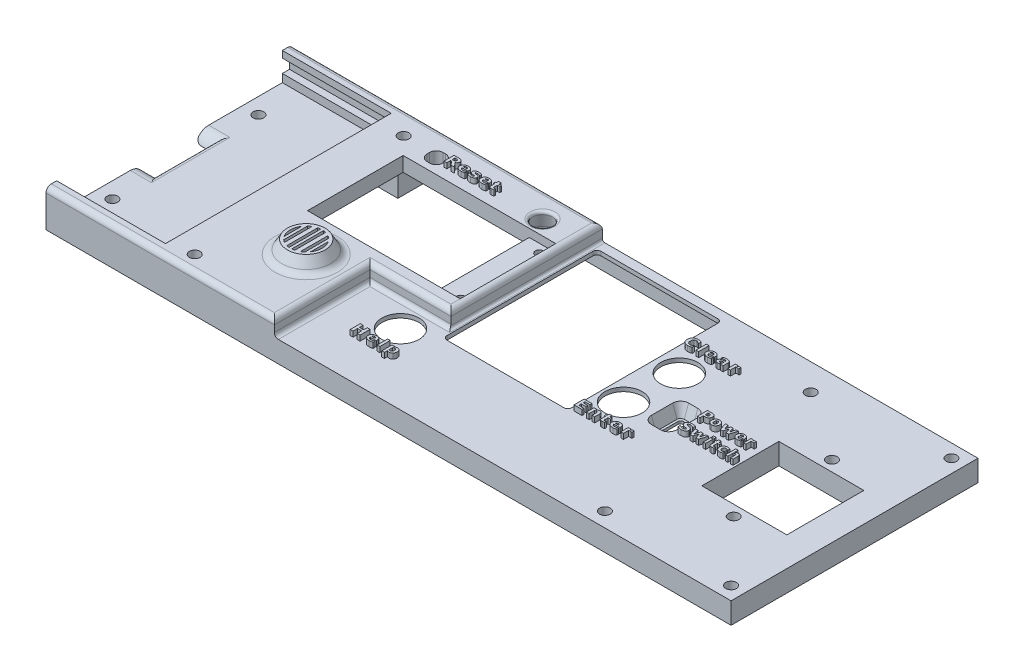
SolidWorks part; units mm, degrees
ref_plane "Front Plane" through (0, 0, 0) normal (0, 0, 1) x (1, 0, 0)
ref_plane "Top Plane" through (0, 0, 0) normal (0, 1, 0) x (1, 0, 0)
ref_plane "Right Plane" through (0, 0, 0) normal (1, 0, 0) x (0, 0, -1)
sketch "Sketch1" plane through (0, 0, 0) normal (0, 1, 0) x (1, 0, 0)
  line L1 (-85, -46.5) -> (85, -46.5)
  line L2 (-85, -46.5) -> (-85, 46.5)
  line L3 (-85, 46.5) -> (85, 46.5)
  line L4 (85, -46.5) -> (85, 46.5)
  line L5 (-85, -46.5) -> (85, 46.5) construction
  line L6 (-85, 46.5) -> (85, -46.5) construction
  point P0 (0, 0)
  dimension "D1" = 170
  dimension "D2" = 93
extrude "Base_01" add sketch "Sketch1" along normal blind 5
sketch "Sketch2" plane through (0, 5, 0) normal (0, 1, 0) x (1, 0, 0)
  line L0 (85, 46.5) -> (-85, 46.5) construction
  line L1 (-10, 46.5) -> (41, 46.5) construction
  line L2 (-10, 46.5) -> (-10, -18.5) construction
  line L3 (-10, -18.5) -> (41, -18.5) construction
  line L4 (41, 46.5) -> (41, -18.5) construction
  line L5 (85, -46.5) -> (85, 46.5) construction
  line L6 (-10, -18.5) -> (41, 46.5) construction
  line L8 (-8, 43) -> (39, 43)
  line L9 (-8, 43) -> (-8, -15)
  line L10 (-8, -15) -> (39, -15)
  line L11 (39, 43) -> (39, -15)
  line L12 (-8, 43) -> (39, -15) construction
  line L13 (-8, -15) -> (39, 43) construction
  point P8 (15.5, 14)
  dimension "D1" = 95
  dimension "D2" = 65
  dimension "D3" = 51
  dimension "D4" = 58
  dimension "D5" = 47
extrude "Keypad" cut sketch "Sketch2" against normal through all
fillet "Keypad_Fillet" radius 1.5 4 edges at (39, 2.5, 15) (-8, 2.5, 15) (-8, 2.5, -43) (39, 2.5, -43)
sketch "Sketch3" plane through (0, 5, 0) normal (0, 1, 0) x (1, 0, 0)
  line L0 (-8, 41.5) -> (-8, -13.5) construction
  line L7 (85, 46.5) -> (-85, 46.5) construction
  line L8 (85, -46.5) -> (85, 46.5) construction
  line L9 (-85, -46.5) -> (85, -46.5) construction
  circle A0 centre (48, 18) radius 7
  circle A1 centre (47, -2) radius 7
  circle A2 centre (-19, -20) radius 7
  point P9 (55, 18)
  point P10 (54, -2)
  point P11 (48, 25)
  point P12 (48, 11)
  point P13 (47, 5)
  point P14 (47, -9)
  point P23 (-26, -20)
  point P26 (-19, -13)
  dimension "D2" = 14
  dimension "D1" = 63
  dimension "D3" = 62
  dimension "D4" = 55.5
  dimension "D5" = 34
  dimension "D6" = 111
  dimension "D7" = 33.5
extrude "Buttons" cut sketch "Sketch3" against normal through all
sketch "Sketch4" plane through (0, 0, 0) normal (0, -1, 0) x (1, 0, 0)
  line L0 (-85, 46.5) -> (85, 46.5) construction
  line L1 (-80, 43) -> (80.5, 43)
  line L2 (-80, 43) -> (-80, -45)
  line L3 (-80, -45) -> (80.5, -45)
  line L4 (80.5, 43) -> (80.5, -45)
  line L5 (85, 46.5) -> (85, -46.5) construction
  line L6 (85, -46.5) -> (-85, -46.5) construction
  line L7 (-85, -46.5) -> (-85, 46.5) construction
  dimension "D1" = 3.5
  dimension "D2" = 4.5
  dimension "D3" = 1.5
  dimension "D4" = 5
extrude "Base_01_Ext_Cut" cut sketch "Sketch4" against normal blind 3.5
sketch "Sketch5" plane through (0, 5, 0) normal (0, 1, 0) x (1, 0, 0)
  line L0 (39, -13.5) -> (39, 41.5) construction
  line L1 (-66, 26.0978) -> (-10, 26.0978) construction
  line L2 (-66, 26.0978) -> (-66, -7.5) construction
  line L3 (-66, -7.5) -> (-10, -7.5) construction
  line L4 (-10, 26.0978) -> (-10, -7.5) construction
  line L5 (85, 46.5) -> (-85, 46.5) construction
  line L6 (-10, 26.0978) -> (-10, 46.5)
  line L7 (-8, 46.5) -> (-8, 41.5691) construction
  line L8 (-8, 41.5) -> (-8, -13.5) construction
  line L9 (-9.5, 46.5) -> (-9.5, -10.5)
  line L10 (-9.5, -10.5) -> (-40, -10.5)
  line L11 (-40, -10.5) -> (-40, -46.5)
  line L12 (-85, -46.5) -> (85, -46.5) construction
  line L13 (-40, -46.5) -> (-85, -46.5)
  line L14 (-85, -46.5) -> (-85, 46.5)
  line L15 (-85, 46.5) -> (-85, -46.5) construction
  line L16 (-85, 46.5) -> (-9.5, 46.5)
  dimension "D1" = 105
  dimension "D2" = 56
  dimension "D3" = 54
  dimension "D4" = 75.5
  dimension "D5" = 3
  dimension "D6" = 45
extrude "Base_02" add sketch "Sketch5" along normal blind 6
fillet "Fillet2" radius 1 1 edges at (-9.5, 5, -18)
fillet "Fillet3" radius 1.5 2 edges at (-40, 5, 28.5) (-24.25, 5, 10.5)
fillet "Base_02_Fillet" radius 2 6 edges at (-62.5, 11, 46.5) (-85, 11, 0) (-47.25, 11, -46.5) (-9.5, 11, -18) (-24.75, 11, 10.5) (-40, 11, 28.5)
sketch "Sketch7" plane through (0, 11, 0) normal (0, 1, 0) x (1, 0, 0)
  line L0 (39, -13.5) -> (39, 41.5) construction
  line L1 (-69, -5) -> (-11.5, -5)
  line L2 (-69, -5) -> (-69, 31)
  line L3 (-69, 31) -> (-11.5, 31)
  line L4 (-11.5, -5) -> (-11.5, 31)
  line L5 (-69, -5) -> (-11.5, 31) construction
  line L6 (-69, 31) -> (-11.5, -5) construction
  line L7 (-65, 33.5) -> (-59, 33.5)
  line L8 (-65, 33.5) -> (-65, 39.5)
  line L9 (-65, 39.5) -> (-59, 39.5)
  line L10 (-59, 33.5) -> (-59, 39.5)
  line L11 (-65, 33.5) -> (-59, 39.5) construction
  line L12 (-65, 39.5) -> (-59, 33.5) construction
  line L13 (-38.5, -46.5) -> (85, -46.5) construction
  line L15 (-85, 46.5) -> (-9.5, 46.5) construction
  line L16 (-85, -46.5) -> (-85, 46.5) construction
  point P0 (-40.25, 13)
  point P5 (-62, 36.5)
  dimension "D1" = 57.5
  dimension "D2" = 108
  dimension "D3" = 36
  dimension "D4" = 77.5
  dimension "D5" = 6
  dimension "D6" = 13
  dimension "D7" = 26
extrude "Display & Reset" cut sketch "Sketch7" against normal through all
fillet "Reset_Fillet" radius 2.5 4 edges at (-65, 7.25, -33.5) (-65, 7.25, -39.5) (-59, 7.25, -33.5) (-59, 7.25, -39.5)
ref_plane "Display Support Plane" through (0, 8, 0) normal (0, 1, 0) x (1, 0, 0)
sketch "Sketch8" plane through (0, 8, 0) normal (0, 1, 0) x (1, 0, 0)
  line L0 (-11.5, 31) -> (-69, 31) construction
  line L1 (-21.5, 31) -> (-11.5, 31)
  line L2 (-21.5, 31) -> (-21.5, -5)
  line L3 (-21.5, -5) -> (-11.5, -5)
  line L4 (-11.5, 31) -> (-11.5, -5)
  dimension "D1" = 10
extrude "Display_Support" add sketch "Sketch8" against normal up to surface (4.5 mm away) up to face at (-40.25, 3.5, -13)
sketch "Sketch10" plane through (0, 8, 0) normal (0, 1, 0) x (1, 0, 0)
  line L1 (-69, 31) -> (-69, -5) construction
  line L2 (-11.5, 31) -> (-69, 31) construction
  line L3 (-11.5, 13) -> (-21.5, 13) construction
  line L4 (-11.5, -5) -> (-11.5, 31) construction
  line L5 (-21.5, 31) -> (-21.5, -5) construction
  circle A0 centre (-14.5, 27.8) radius 1.5
  circle A2 centre (-14.5, -1.8) radius 1.5
  point P6 (-13, 27.8)
  point P7 (-14.5, 26.3)
  dimension "D1" = 3
  dimension "D2" = 4.7
  dimension "5.5" = 56
extrude "Display Support holes" cut sketch "Sketch10" against normal through all
sketch "Sketch9" plane through (0, 3.5, 0) normal (0, -1, 0) x (1, 0, 0)
  line L0 (-9.5, -45) -> (-80, -45)
  line L1 (-80, -45) -> (80.5, -45) construction
  line L2 (-80, -45) -> (-80, 43)
  line L3 (80.5, 43) -> (-80, 43) construction
  line L4 (-80, 43) -> (-80, -45) construction
  line L5 (-80, 43) -> (-40, 43)
  line L6 (-9.5, 10.5) -> (-40, 10.5)
  line L7 (-40, 10.5) -> (-40, 46.5)
  line L8 (-40, 46.5) -> (-85, 46.5)
  line L9 (-85, 46.5) -> (-85, -46.5)
  line L10 (-85, -46.5) -> (-9.5, -46.5)
  line L11 (-9.5, -46.5) -> (-9.5, 10.5)
  line L12 (-9.5, 10.5) -> (-40, 10.5)
  line L17 (-9.5, -46.5) -> (-9.5, 10.5)
  line L18 (-40, 43) -> (-40, 10.5)
  line M7 (-69, 5) -> (-21.5, 5)
  line M8 (-21.5, 5) -> (-21.5, -31)
  line M9 (-21.5, -31) -> (-69, -31)
  line M10 (-69, -31) -> (-69, 5)
  line M11 (-59, -36) -> (-59, -37)
  arc M12 (-59, -37) -> (-61.5, -39.5) centre (-61.5, -37) cw
  line M13 (-61.5, -39.5) -> (-62.5, -39.5)
  arc M14 (-62.5, -39.5) -> (-65, -37) centre (-62.5, -37) cw
  line M15 (-65, -37) -> (-65, -36)
  arc M16 (-65, -36) -> (-62.5, -33.5) centre (-62.5, -36) cw
  line M17 (-62.5, -33.5) -> (-61.5, -33.5)
  arc M18 (-61.5, -33.5) -> (-59, -36) centre (-61.5, -36) cw
  line M22 (-80, 43) -> (-80, -45)
  line M23 (-80, -45) -> (80.5, -45)
  line M25 (80.5, 43) -> (-80, 43)
  dimension "D1" = 0
extrude "Base_02_Ext_Cut" cut sketch "Sketch9" against normal blind 2 contours L18 L17 L12 M25 M22 M23 M18 M11 M12 M13 M14 M15 M16 M17 M10 M7 M8 M9
sketch "Sketch11" plane through (0, 11, 0) normal (0, 1, 0) x (1, 0, 0)
  line L0 (-40, -46.5) -> (-85, -46.5) construction
  line L1 (-85, -46.5) -> (-85, 46.5) construction
  line L2 (-55, -13.5) -> (-55, -25.5) construction
  line L3 (-54.5, -13.5209) -> (-54.5, -25.4791)
  line L4 (-52, -14.3038) -> (-52, -24.6962)
  line L5 (-50, -16.1834) -> (-50, -22.8166)
  line L6 (-53.5, -13.6905) -> (-53.5, -25.3095)
  line L7 (-51, -15.0279) -> (-51, -23.9721)
  line L8 (-60, -16.1834) -> (-60, -22.8166)
  line L9 (-59, -15.0279) -> (-59, -23.9721)
  line L10 (-58, -14.3038) -> (-58, -24.6962)
  line L11 (-56.5, -13.6905) -> (-56.5, -25.3095)
  line L12 (-55.5, -13.5209) -> (-55.5, -25.4791)
  arc A0 (-51, -15.0279) -> (-52, -14.3038) centre (-55, -19.5) ccw
  arc A1 (-50, -22.8166) -> (-50, -16.1834) centre (-55, -19.5) ccw
  arc A2 (-52, -24.6962) -> (-51, -23.9721) centre (-55, -19.5) ccw
  arc A3 (-53.5, -13.6905) -> (-54.5, -13.5209) centre (-55, -19.5) ccw
  arc A4 (-55.5, -13.5209) -> (-56.5, -13.6905) centre (-55, -19.5) ccw
  arc A5 (-54.5, -25.4791) -> (-53.5, -25.3095) centre (-55, -19.5) ccw
  arc A6 (-56.5, -25.3095) -> (-55.5, -25.4791) centre (-55, -19.5) ccw
  arc A7 (-59, -23.9721) -> (-58, -24.6962) centre (-55, -19.5) ccw
  arc A8 (-60, -16.1834) -> (-60, -22.8166) centre (-55, -19.5) ccw
  arc A9 (-58, -14.3038) -> (-59, -15.0279) centre (-55, -19.5) ccw
  point P2 (-55, -13.5)
  point P5 (-49, -19.5)
  dimension "D3" = 12
  dimension "D1" = 33
  dimension "D2" = 36
  dimension "D4" = 0.5
  dimension "D5" = 2.5
  dimension "D6" = 1
  dimension "D7" = 1
  dimension "D8" = 2
extrude "Cut-Extrude7" cut sketch "Sketch11" against normal through all contours L3 A5 L6 A3 | L4 A2 L7 A0 | L5 A1 | L11 A6 L12 A4 | L10 A9 L9 A7 | L8 A8
ref_plane "Support Speaker Plane" through (0, 0, 0) normal (0, -1, 0) x (-1, 0, 0)
sketch "Sketch15" plane through (0, 11, 0) normal (0, 1, 0) x (1, 0, 0)
  circle A0 centre (-55, -19.5) radius 10
  point P0 (-55, -19.5)
  dimension "D1" = 20
extrude "Speaker_Extrude" add sketch "Sketch15" along normal blind 5 draft 30
sketch "Sketch16" plane through (0, 16, 0) normal (0, 1, 0) x (1, 0, 0)
  line L1 (-50, -16.1834) -> (-50, -22.8166)
  line L2 (-50, -16.1834) -> (-50, -22.8166)
  line L3 (-60, -22.8166) -> (-60, -16.1834)
  line L4 (-56.5, -13.6905) -> (-56.5, -25.3095)
  line L5 (-55.5, -25.4791) -> (-55.5, -13.5209)
  line L6 (-56.5, -13.6905) -> (-56.5, -25.3095)
  line L7 (-55.5, -25.4791) -> (-55.5, -13.5209)
  line L8 (-59, -15.0279) -> (-59, -23.9721)
  line L9 (-58, -24.6962) -> (-58, -14.3038)
  line L10 (-59, -15.0279) -> (-59, -23.9721)
  line L11 (-58, -24.6962) -> (-58, -14.3038)
  line L12 (-60, -22.8166) -> (-60, -16.1834)
  line L14 (-51, -23.9721) -> (-51, -15.0279)
  line L15 (-52, -14.3038) -> (-52, -24.6962)
  line L16 (-51, -23.9721) -> (-51, -15.0279)
  line L17 (-52, -14.3038) -> (-52, -24.6962)
  line L18 (-53.5, -25.3095) -> (-53.5, -13.6905)
  line L19 (-54.5, -13.5209) -> (-54.5, -25.4791)
  line L20 (-53.5, -25.3095) -> (-53.5, -13.6905)
  line L21 (-54.5, -13.5209) -> (-54.5, -25.4791)
  arc A1 (-50, -22.8166) -> (-50, -16.1834) centre (-55, -19.5) ccw
  arc A2 (-50, -22.8166) -> (-50, -16.1834) centre (-55, -19.5) ccw
  arc A3 (-60, -16.1834) -> (-60, -22.8166) centre (-55, -19.5) ccw
  arc A4 (-56.5, -25.3095) -> (-55.5, -25.4791) centre (-55, -19.5) ccw
  arc A5 (-55.5, -13.5209) -> (-56.5, -13.6905) centre (-55, -19.5) ccw
  arc A6 (-56.5, -25.3095) -> (-55.5, -25.4791) centre (-55, -19.5) ccw
  arc A7 (-55.5, -13.5209) -> (-56.5, -13.6905) centre (-55, -19.5) ccw
  arc A8 (-59, -23.9721) -> (-58, -24.6962) centre (-55, -19.5) ccw
  arc A9 (-58, -14.3038) -> (-59, -15.0279) centre (-55, -19.5) ccw
  arc A10 (-59, -23.9721) -> (-58, -24.6962) centre (-55, -19.5) ccw
  arc A11 (-58, -14.3038) -> (-59, -15.0279) centre (-55, -19.5) ccw
  arc A12 (-60, -16.1834) -> (-60, -22.8166) centre (-55, -19.5) ccw
  arc A14 (-52, -24.6962) -> (-51, -23.9721) centre (-55, -19.5) ccw
  arc A15 (-51, -15.0279) -> (-52, -14.3038) centre (-55, -19.5) ccw
  arc A16 (-52, -24.6962) -> (-51, -23.9721) centre (-55, -19.5) ccw
  arc A17 (-51, -15.0279) -> (-52, -14.3038) centre (-55, -19.5) ccw
  arc A18 (-54.5, -25.4791) -> (-53.5, -25.3095) centre (-55, -19.5) ccw
  arc A19 (-53.5, -13.6905) -> (-54.5, -13.5209) centre (-55, -19.5) ccw
  arc A20 (-54.5, -25.4791) -> (-53.5, -25.3095) centre (-55, -19.5) ccw
  arc A21 (-53.5, -13.6905) -> (-54.5, -13.5209) centre (-55, -19.5) ccw
  dimension "D1" = 0
  dimension "D2" = 0
  dimension "D3" = 0
  dimension "D4" = 0
  dimension "D5" = 0
  dimension "D6" = 0
extrude "Grid_Ext_Cut" cut sketch "Sketch16" against normal through all
sketch "Sketch17" plane through (0, 5.5, 0) normal (0, -1, 0) x (1, 0, 0)
  circle A1 centre (-55, 19.5) radius 10
  circle A2 centre (-55, 19.5) radius 10
  dimension "D1" = 0
extrude "Lower_Side_Cut" cut sketch "Sketch17" against normal blind 3 draft 35 draft outward yes
fillet "Side_Fillet" radius 3 1 edges at (-55, 11, 29.5)
sketch "Sketch24" plane through (0, 8.5, 0) normal (0, -1, 0) x (1, 0, 0)
  circle A0 centre (-55, 19.5) radius 7.5
  circle A1 centre (-55, 19.5) radius 10
  circle A2 centre (-55, 19.5) radius 10 construction
  line M3 (-52, 14.3038) -> (-52, 24.6962)
  arc M4 (-52, 24.6962) -> (-51, 23.9721) centre (-55, 19.5) cw
  line M5 (-51, 23.9721) -> (-51, 15.0279)
  arc M6 (-51, 15.0279) -> (-52, 14.3038) centre (-55, 19.5) cw
  line M7 (-56.5, 13.6905) -> (-56.5, 25.3095)
  arc M8 (-56.5, 25.3095) -> (-55.5, 25.4791) centre (-55, 19.5) cw
  line M9 (-55.5, 25.4791) -> (-55.5, 13.5209)
  arc M10 (-55.5, 13.5209) -> (-56.5, 13.6905) centre (-55, 19.5) cw
  arc M11 (-58, 14.3038) -> (-59, 15.0279) centre (-55, 19.5) cw
  line M12 (-59, 15.0279) -> (-59, 23.9721)
  arc M13 (-59, 23.9721) -> (-58, 24.6962) centre (-55, 19.5) cw
  line M14 (-58, 24.6962) -> (-58, 14.3038)
  arc M15 (-60, 16.1834) -> (-60, 22.8166) centre (-55, 19.5) cw
  line M16 (-60, 22.8166) -> (-60, 16.1834)
  line M18 (-50, 16.1834) -> (-50, 22.8166)
  arc M19 (-50, 22.8166) -> (-50, 16.1834) centre (-55, 19.5) cw
  line M20 (-54.5, 13.5209) -> (-54.5, 25.4791)
  arc M21 (-54.5, 25.4791) -> (-53.5, 25.3095) centre (-55, 19.5) cw
  line M22 (-53.5, 25.3095) -> (-53.5, 13.6905)
  arc M23 (-53.5, 13.6905) -> (-54.5, 13.5209) centre (-55, 19.5) cw
  dimension "D2" = 15
  dimension "D1" = 0
extrude "Cut-Extrude13" cut sketch "Sketch24" against normal offset from surface (6.5 mm away) 1 contours A0 M6 M3 M4 M5 M10 M7 M8 M9 M14 M11 M12 M13 M16 M15 M23 M20 M21 M22 M19 M18 up to face at (-49.5, 16, 19.5)
fillet "Fillet7" radius 5 1 edges at (-55, 8.5, 12)
fillet "Fillet8" radius 1 1 edges at (-55, 5.5, 9.5)
sketch "Sketch18" plane through (0, 11, 0) normal (0, 1, 0) x (1, 0, 0)
  line L2 (-59, 36) -> (-59, 37) construction
  line L3 (39, -13.5) -> (39, 41.5) construction
  circle A0 centre (-22, 36.5) radius 3.5
  point P4 (-18.5, 36.5)
  point P8 (-59, 36.5)
  point P9 (-25.5, 36.5)
  dimension "D2" = 7
  dimension "D1" = 64.5
extrude "Indicator" cut sketch "Sketch18" against normal up to surface (5.5 mm away) draft 10
sketch "Sketch20" plane through (0, 5, 0) normal (0, 1, 0) x (1, 0, 0)
  line L0 (-38.5, -46.5) -> (85, -46.5) construction
  line L1 (59, 7.5) -> (63.5, 7.5)
  line L2 (59, 7.5) -> (59, -1.5)
  line L3 (59, -1.5) -> (63.5, -1.5)
  line L4 (63.5, 7.5) -> (63.5, -1.5)
  line L5 (59, 7.5) -> (63.5, -1.5) construction
  line L6 (59, -1.5) -> (63.5, 7.5) construction
  line L7 (85, -46.5) -> (85, 46.5) construction
  point P0 (59, 3)
  dimension "D4" = 26
  dimension "D1" = 54
  dimension "D2" = 9
  dimension "D3" = 4.5
extrude "Power Switch" cut sketch "Sketch20" against normal through all
sketch "Sketch25" plane through (85, 0, 0) normal (1, 0, 0) x (0, 0, -1)
  line L4 (-46.5, 0) -> (46.5, 0)
  line L5 (46.5, 0) -> (46.5, 5)
  line L6 (46.5, 5) -> (-46.5, 5)
  line L7 (-46.5, 5) -> (-46.5, 0)
  line L9 (46.5, 0) -> (46.5, 5)
  line L10 (46.5, 5) -> (-46.5, 5)
  line L11 (-46.5, 5) -> (-46.5, 0)
  line L13 (-46.5, 0) -> (46.5, 0)
  dimension "D1" = 0
extrude "Base_Support_01" add sketch "Sketch25" along normal blind 2
sketch "Sketch26" plane through (0, 0, 0) normal (0, -1, 0) x (1, 0, 0)
  line L0 (-80, -45) -> (80.5, -45) construction
  line L1 (-9.5, -45) -> (80.5, -45) construction
  line L2 (80.5, -45) -> (80.5, 43) construction
  line L3 (80.5, 43) -> (-80, 43) construction
  line L4 (-85, -46.5) -> (87, -46.5)
  line L5 (87, -46.5) -> (87, 46.5)
  line L6 (87, 46.5) -> (-85, 46.5)
  line L7 (-85, 46.5) -> (-85, -46.5)
  line L8 (-85, -46.5) -> (87, -46.5)
  line L10 (87, 46.5) -> (-85, 46.5)
  line L11 (-85, 46.5) -> (-85, -46.5)
  line L12 (-80, 43) -> (-80, -45) construction
  line L13 (-80, -45) -> (80.5, -45)
  line L14 (-9.5, -45) -> (80.5, -45)
  line L15 (80.5, -45) -> (80.5, 43)
  line L16 (80.5, 43) -> (-80, 43)
  line L17 (-80, 43) -> (-80, -45)
  line L23 (87, -46.5) -> (87, 46.5)
  line M5 (-80, -45) -> (-80, 43)
  line M6 (-80, 43) -> (80.5, 43)
  line M7 (80.5, 43) -> (80.5, -45)
  line M8 (80.5, -45) -> (-80, -45)
  line M9 (-85, -46.5) -> (87, -46.5)
  line M10 (87, -46.5) -> (87, 46.5)
  line M11 (87, 46.5) -> (-85, 46.5)
  line M12 (-85, 46.5) -> (-85, -46.5)
  dimension "D1" = 0
extrude "Base_Support_02" add sketch "Sketch26" along normal blind 3 contours L13 M12 M9 M10 M11 M8 M5 M6 M7
sketch "Sketch28" plane through (0, -3, 0) normal (0, -1, 0) x (1, 0, 0)
  line L10 (80.5, 43) -> (74.5, 43)
  line L11 (80.5, 43) -> (80.5, 23)
  line L12 (80.5, 23) -> (74.5, 23)
  line L13 (74.5, 43) -> (74.5, 23)
  line L14 (80.5, -45) -> (74.5, -45)
  line L15 (80.5, -45) -> (80.5, -25)
  line L16 (80.5, -25) -> (74.5, -25)
  line L17 (74.5, -45) -> (74.5, -25)
  dimension "D1" = 6
  dimension "D2" = 20
  dimension "D3" = 20
  dimension "D4" = 6
extrude "Right Side Hole Support" add sketch "Sketch28" against normal up to surface (6.5 mm away) up to face at (61.25, 3.5, -3)
sketch "Sketch29" plane through (0, -3, 0) normal (0, -1, 0) x (1, 0, 0)
  line L0 (-85, 46.5) -> (-85, -46.5) construction
  line L5 (-80, -45) -> (-70, -45)
  line L6 (-80, -45) -> (-80, -30)
  line L7 (-80, -30) -> (-70, -30)
  line L8 (-70, -45) -> (-70, -30)
  line L10 (-80, 43) -> (-70, 43)
  line L11 (-80, 43) -> (-80, 31)
  line L12 (-80, 31) -> (-70, 31)
  line L13 (-70, 43) -> (-70, 31)
  dimension "D1" = 15
  dimension "D2" = 15
  dimension "D3" = 15
  dimension "D4" = 12
extrude "Left Side Hole Support" add sketch "Sketch29" against normal up to surface (8.5 mm away) up to face at (-22, 5.5, -40.9698)
sketch "Sketch31" plane through (0, -3, 0) normal (0, -1, 0) x (1, 0, 0)
  line L0 (87, -46.5) -> (87, 46.5) construction
  line L1 (87, 0) -> (-85, 0) construction
  line L2 (-85, 46.5) -> (-85, -46.5) construction
  line L3 (-85, -46.5) -> (87, -46.5) construction
  line L4 (87, 46.5) -> (-85, 46.5) construction
  circle A0 centre (79, 41) radius 2
  circle A2 centre (-76, 40.5) radius 2
  circle A5 centre (79, -36.5) radius 2
  circle A6 centre (-75.3, -37.5) radius 2
  point P7 (79, 39)
  point P8 (77, 41)
  point P14 (77, -36.5)
  point P15 (-74, 40.5)
  point P16 (79, -34.5)
  point P21 (-76, 38.5)
  point P24 (-75.3, -35.5)
  point P25 (-73.3, -37.5)
  dimension "D1" = 4
  dimension "D2" = 10
  dimension "D3" = 11
  dimension "D4" = 12
  dimension "D5" = 7.5
  dimension "D6" = 8
  dimension "D7" = 11
  dimension "D8" = 11.7
extrude "Holes" cut sketch "Sketch31" against normal through all
sketch "Sketch33" plane through (0, 3.5, 0) normal (0, -1, 0) x (1, 0, 0)
  line L0 (59, -7.5) -> (63.5, 1.5) construction
  line L1 (59, 1.5) -> (63.5, -7.5) construction
  line L3 (56.25, -12.5) -> (66.25, -12.5)
  line L4 (59, -7.5) -> (63.5, -7.5)
  line L5 (63.5, -7.5) -> (63.5, 1.5)
  line L6 (63.5, 1.5) -> (59, 1.5)
  line L7 (59, 1.5) -> (59, -7.5)
  line L8 (59, -7.5) -> (63.5, -7.5) construction
  line L9 (63.5, -7.5) -> (63.5, 1.5) construction
  line L10 (63.5, 1.5) -> (59, 1.5) construction
  line L11 (59, 1.5) -> (59, -7.5) construction
  line L12 (56.25, -12.5) -> (56.25, 6.5)
  line L13 (56.25, 6.5) -> (66.25, 6.5)
  line L14 (66.25, -12.5) -> (66.25, 6.5)
  line L15 (56.25, -12.5) -> (66.25, 6.5) construction
  line L16 (56.25, 6.5) -> (66.25, -12.5) construction
  point P2 (61.25, -3)
  dimension "D2" = 10
  dimension "D3" = 19
  dimension "D1" = 0
extrude "Power Switch Lower Support" add sketch "Sketch33" along normal offset from surface (4 mm away) 2.5 up to face at (-76, -3, 38.5)
sketch "Sketch34" plane through (0, 3.5, 0) normal (0, 1, 0) x (1, 0, 0)
  line L4 (63.5, -1.5) -> (63.5, 7.5)
  line L5 (63.5, 7.5) -> (59, 7.5)
  line L6 (59, 7.5) -> (59, -1.5)
  line L7 (59, -1.5) -> (63.5, -1.5)
  line L8 (63.5, -1.5) -> (63.5, 7.5)
  line L9 (63.5, 7.5) -> (59, 7.5)
  line L10 (59, 7.5) -> (59, -1.5)
  line L11 (59, -1.5) -> (63.5, -1.5)
  dimension "D1" = 0
extrude "Lower Support Cut" cut sketch "Sketch34" against normal through all both and the other way through all
sketch "Sketch22" plane through (0, 5, 0) normal (0, 1, 0) x (1, 0, 0)
  line L0 (59, 7.5) -> (63.5, -1.5) construction
  line L1 (63.5, 7.5) -> (59, -1.5) construction
  line L2 (59, 7.5) -> (59, -1.5) construction
  line L3 (59.5, -4) -> (63, -4)
  line L4 (56.5, -1) -> (56.5, 7)
  line L5 (59.5, 10) -> (63, 10)
  line L6 (66, -1) -> (66, 7)
  line L7 (56.5, -4) -> (66, 10) construction
  line L8 (56.5, 10) -> (66, -4) construction
  line L9 (59, -1.5) -> (63.5, -1.5) construction
  arc A0 (56.5, 7) -> (59.5, 10) centre (59.5, 7) cw
  arc A1 (63, -4) -> (66, -1) centre (63, -1) ccw
  arc A2 (63, 10) -> (66, 7) centre (63, 7) cw
  arc A3 (59.5, -4) -> (56.5, -1) centre (59.5, -1) cw
  point P8 (61.25, 3)
  dimension "D3" = 3
  dimension "D1" = 2.5
  dimension "D2" = 2.5
extrude "Upper Suppoet CUt" cut sketch "Sketch22" against normal blind 4.5 draft 20
fillet "Switch Support FIllet" radius 1 4 edges at (59, 0, -7.5) (63.5, 0, -7.5) (63.5, 0, 1.5) (59, 0, 1.5)
sketch "Sketch35" plane through (-85, 0, 0) normal (-1, 0, 0) x (0, 0, 1)
  line L0 (-46.5, 9) -> (-46.5, -3) construction
  line L1 (46.5, -3) -> (-46.5, -3) construction
  line L2 (46.5, 9) -> (46.5, -3) construction
  line L3 (-44.5, 11) -> (44.5, 11) construction
  line L4 (-46.5, 9) -> (-46.5, -3)
  line L5 (46.5, -3) -> (-46.5, -3)
  line L6 (46.5, 9) -> (46.5, -3)
  line L7 (-44.5, 11) -> (-42.5, 11)
  line L8 (42.5, 11) -> (42.5, 0.5)
  line L9 (-42.5, 11) -> (-42.5, 0.5)
  line L10 (-42.5, 0.5) -> (42.5, 0.5)
  line L11 (42.5, 11) -> (44.5, 11)
  arc A0 (46.5, 9) -> (44.5, 11) centre (44.5, 9) ccw construction
  arc A1 (-44.5, 11) -> (-46.5, 9) centre (-44.5, 9) ccw construction
  arc A2 (46.5, 9) -> (44.5, 11) centre (44.5, 9) ccw
  arc A3 (-44.5, 11) -> (-46.5, 9) centre (-44.5, 9) ccw
  dimension "D1" = 4
  dimension "D2" = 4
  dimension "D3" = 3.5
extrude "Base 03" add sketch "Sketch35" along normal blind 34
sketch "Sketch36" plane through (-119, 0, 0) normal (-1, 0, 0) x (0, 0, 1)
  line L0 (-42.5, 0.5) -> (-42.5, 11) construction
  line L1 (-42.5, 8.5) -> (-45.2, 8.5)
  line L2 (-42.5, 8.5) -> (-42.5, 3.5)
  line L3 (-42.5, 3.5) -> (-45.2, 3.5)
  line L4 (-45.2, 8.5) -> (-45.2, 3.5)
  line L5 (-42.5, 11) -> (-44.5, 11) construction
  line L7 (0, -3) -> (0, 9) construction
  line L8 (-46.5, -3) -> (46.5, -3) construction
  line L9 (42.5, 9) -> (-42.5, 9) construction
  line L10 (42.5, 3.5) -> (45.2, 3.5)
  line L11 (45.2, 8.5) -> (45.2, 3.5)
  line L12 (42.5, 8.5) -> (45.2, 8.5)
  line L13 (42.5, 8.5) -> (42.5, 3.5)
  point P6 (-42.5, 6)
  dimension "D1" = 5
  dimension "D2" = 5
  dimension "D3" = 2.7
extrude "Camera Holder Ext. Cut" cut sketch "Sketch36" against normal up to surface (34 mm away) up to face at (-85, 4.75, 0)
sketch "Sketch37" plane through (-85, 0, 0) normal (1, 0, 0) x (0, 0, -1)
  line L3 (-46.5, 9) -> (-42.5, 9)
  line L4 (-42.5, 9) -> (-42.5, 11)
  line L5 (-42.5, 11) -> (-44.5, 11)
  line L6 (-46.5, 9) -> (-42.5, 9)
  line L7 (-42.5, 9) -> (-42.5, 11)
  line L8 (-42.5, 11) -> (-44.5, 11)
  line L9 (42.5, 9) -> (46.5, 9)
  line L10 (44.5, 11) -> (42.5, 11)
  line L11 (42.5, 11) -> (42.5, 9)
  line L12 (42.5, 9) -> (46.5, 9)
  line L13 (44.5, 11) -> (42.5, 11)
  line L14 (42.5, 11) -> (42.5, 9)
  arc A1 (-44.5, 11) -> (-46.5, 9) centre (-44.5, 9) ccw
  arc A2 (-44.5, 11) -> (-46.5, 9) centre (-44.5, 9) ccw
  arc A3 (46.5, 9) -> (44.5, 11) centre (44.5, 9) ccw
  arc A4 (46.5, 9) -> (44.5, 11) centre (44.5, 9) ccw
  dimension "D1" = 0
  dimension "D2" = 0
extrude "Tuned side gaps" add sketch "Sketch37" along normal up to surface (2 mm away)
ref_plane "Plane3" through (-85, 0, 0) normal (-1, 0, 0) x (0, 0, 1)
sketch "Sketch38" plane through (-85, 0, 0) normal (-1, 0, 0) x (0, 0, 1)
  line L0 (42.5, 11) -> (42.5, 8.5) construction
  line L1 (-42.5, 9) -> (-42.5, 11) construction
  line L2 (-42.5, 11) -> (42.5, 11) construction
  line L3 (42.5, 9) -> (-42.5, 9) construction
  line L4 (42.5, 11) -> (42.5, 9)
  line L5 (-42.5, 9) -> (-42.5, 11)
  line L6 (-42.5, 11) -> (42.5, 11)
  line L7 (42.5, 9) -> (-42.5, 9)
extrude "Camera Holder Support Cut" add sketch "Sketch38" against normal up to surface (2 mm away)
sketch "Sketch39" plane through (-119, 0, 0) normal (-1, 0, 0) x (0, 0, 1)
  line L16 (-45.2, 8.5) -> (-42.5, 8.5)
  line L17 (-42.5, 8.5) -> (-42.5, 11)
  line L18 (-42.5, 11) -> (-44.5, 11)
  line L19 (-46.5, 9) -> (-46.5, -3)
  line L20 (-46.5, -3) -> (46.5, -3)
  line L21 (46.5, -3) -> (46.5, 9)
  line L22 (44.5, 11) -> (42.5, 11)
  line L23 (42.5, 11) -> (42.5, 8.5)
  line L24 (42.5, 8.5) -> (45.2, 8.5)
  line L25 (45.2, 8.5) -> (45.2, 3.5)
  line L26 (45.2, 3.5) -> (42.5, 3.5)
  line L27 (42.5, 3.5) -> (42.5, 0.5)
  line L28 (42.5, 0.5) -> (-42.5, 0.5)
  line L29 (-42.5, 0.5) -> (-42.5, 3.5)
  line L30 (-42.5, 3.5) -> (-45.2, 3.5)
  line L31 (-45.2, 3.5) -> (-45.2, 8.5)
  line L32 (-45.2, 8.5) -> (-42.5, 8.5)
  line L33 (-42.5, 8.5) -> (-42.5, 11)
  line L34 (-42.5, 11) -> (-44.5, 11)
  line L35 (-46.5, 9) -> (-46.5, -3)
  line L36 (-46.5, -3) -> (46.5, -3)
  line L37 (46.5, -3) -> (46.5, 9)
  line L38 (44.5, 11) -> (42.5, 11)
  line L39 (42.5, 11) -> (42.5, 8.5)
  line L40 (42.5, 8.5) -> (45.2, 8.5)
  line L41 (45.2, 8.5) -> (45.2, 3.5)
  line L42 (45.2, 3.5) -> (42.5, 3.5)
  line L43 (42.5, 3.5) -> (42.5, 0.5)
  line L44 (42.5, 0.5) -> (-42.5, 0.5)
  line L45 (-42.5, 0.5) -> (-42.5, 3.5)
  line L46 (-42.5, 3.5) -> (-45.2, 3.5)
  line L47 (-45.2, 3.5) -> (-45.2, 8.5)
  arc A2 (-44.5, 11) -> (-46.5, 9) centre (-44.5, 9) ccw
  arc A3 (46.5, 9) -> (44.5, 11) centre (44.5, 9) ccw
  arc A4 (-44.5, 11) -> (-46.5, 9) centre (-44.5, 9) ccw
  arc A5 (46.5, 9) -> (44.5, 11) centre (44.5, 9) ccw
  dimension "D1" = 0
extrude "base 03 extrude" add sketch "Sketch39" along normal blind 7
sketch "Sketch40" plane through (0, 0.5, 0) normal (0, 1, 0) x (1, 0, 0)
  line L0 (-126, 42.5) -> (-85, 42.5) construction
  line L1 (-126, -42.5) -> (-126, 42.5) construction
  line L2 (-126, -42.5) -> (-85, -42.5) construction
  circle A0 centre (-120, 27.5) radius 2
  circle A1 centre (-120, -27.5) radius 2
  dimension "D3" = 4
  dimension "D1" = 15
  dimension "D2" = 6
  dimension "D4" = 15
extrude "Camera Holding Holes" cut sketch "Sketch40" against normal through all
sketch "Sketch41" plane through (0, 0.5, 0) normal (0, 1, 0) x (1, 0, 0)
  line L0 (-126, -42.5) -> (-126, 42.5) construction
  line L1 (-126, -10) -> (-120, -10)
  line L2 (-126, -10) -> (-126, 10)
  line L3 (-126, 10) -> (-120, 10)
  line L4 (-120, -10) -> (-120, 10)
  line L5 (-126, -10) -> (-120, 10) construction
  line L6 (-126, 10) -> (-120, -10) construction
  line L7 (-85, -42.5) -> (-85, 42.5) construction
  line L8 (-85, -42.5) -> (-85, 42.5) construction
  point P0 (-123, 0)
  point P10 (-85, 0)
  dimension "D1" = 35
  dimension "D3" = 20
extrude "Slit For camera wire" cut sketch "Sketch41" against normal through all
fillet "Fillet10" radius 2 2 edges at (-120, 0.5, 0) (-120, -3, 0)
fillet "Fillet11" radius 5 2 edges at (-122, 0.5, -10) (-122, 0.5, 10)
fillet "Fillet12" radius 2 1 edges at (-126, -3, -28.25)
sketch "Sketch42" plane through (87, 0, 0) normal (1, 0, 0) x (0, 0, -1)
  line L4 (-46.5, 5) -> (-46.5, -3)
  line L5 (-46.5, -3) -> (46.5, -3)
  line L6 (46.5, -3) -> (46.5, 5)
  line L7 (46.5, 5) -> (-46.5, 5)
  line L8 (-46.5, 5) -> (-46.5, -3)
  line L9 (-46.5, -3) -> (46.5, -3)
  line L10 (46.5, -3) -> (46.5, 5)
  line L11 (46.5, 5) -> (-46.5, 5)
  dimension "D1" = 0
extrude "Base Extrude" add sketch "Sketch42" along normal blind 45
sketch "Sketch43" plane through (0, -3, 0) normal (0, -1, 0) x (1, 0, 0)
  line L0 (89, 46.5) -> (89, -46.5) construction
  line L1 (132, 46.5) -> (-126, 46.5) construction
  line L2 (-124, -46.5) -> (132, -46.5) construction
  line L3 (132, 46.5) -> (132, -46.5) construction
  line L5 (89, -14.5) -> (121, -14.5)
  line L6 (89, -14.5) -> (89, 14.5)
  line L7 (89, 14.5) -> (121, 14.5)
  line L8 (121, -14.5) -> (121, 14.5)
  line L9 (89, -14.5) -> (121, 14.5) construction
  line L10 (89, 14.5) -> (121, -14.5) construction
  point P8 (105, 0)
  point P15 (89, 0)
  dimension "D1" = 43
  dimension "D2" = 32
  dimension "D3" = 29
extrude "Phone Ext. Cut" cut sketch "Sketch43" against normal through all
sketch "Sketch44" plane through (0, -3, 0) normal (0, -1, 0) x (1, 0, 0)
  line L0 (132, 46.5) -> (-126, 46.5) construction
  line L5 (132, 46.5) -> (132, -46.5) construction
  line L7 (89, 0) -> (121, 0) construction
  line L11 (89, -14.5) -> (121, -14.5)
  line L12 (121, -14.5) -> (121, 14.5)
  line L13 (121, 14.5) -> (89, 14.5)
  line L14 (89, 14.5) -> (89, -14.5)
  line L15 (89, -14.5) -> (121, -14.5) construction
  line L16 (121, -14.5) -> (121, 14.5) construction
  line L17 (121, 14.5) -> (89, 14.5) construction
  line L18 (89, 14.5) -> (89, -14.5) construction
  circle A0 centre (105, 18.5) radius 2
  circle A1 centre (105, -18.5) radius 2
  circle A2 centre (127, 41.5) radius 2
  circle A3 centre (127, -41.5) radius 2
  point P3 (105, 0)
  point P4 (105, 20.5)
  dimension "D3" = 4
  dimension "D4" = 4
  dimension "D2" = 6
  dimension "D5" = 5
  dimension "D6" = 5
  dimension "D1" = 0
extrude "Phone and box Holes" cut sketch "Sketch44" against normal through all
sketch "Sketch46" plane through (0, -3, 0) normal (0, -1, 0) x (1, 0, 0)
  line L0 (121, -14.5) -> (121, 14.5) construction
  line L1 (121, -12.5) -> (130, -12.5)
  line L2 (121, -12.5) -> (121, 12.5)
  line L3 (121, 12.5) -> (130, 12.5)
  line L4 (130, -12.5) -> (130, 12.5)
  line L5 (121, -12.5) -> (130, 12.5) construction
  line L6 (121, 12.5) -> (130, -12.5) construction
  point P0 (125.5, 0)
  point P5 (121, 0)
  dimension "D1" = 9
  dimension "D2" = 25
extrude "Phone Wire Clearance Cut" cut sketch "Sketch46" against normal blind 6
sketch "Sketch47" plane through (0, 5.5, 0) normal (0, -1, 0) x (1, 0, 0)
  circle A0 centre (-22, -36.5) radius 4.4698 construction
  circle A1 centre (-22, -36.5) radius 4.4698
extrude "Extrude-Thin1" add sketch "Sketch47" along normal blind 1 draft 7 thin
fillet "Fillet13" radius 1 1 edges at (-22, 11, -33)
fillet "Fillet14" radius 2 3 edges at (-40, 5.5, 26.75) (-24.75, 5.5, 10.5) (-9.5, 5.5, -17.25)
sketch "Sketch53" plane through (0, 5, 0) normal (0, 1, 0) x (1, 0, 0)
  line L0 (66, -1) -> (66, 7) construction
  text T0 "Power\r\nSwitch" font "Verdana" height in points 14
  dimension "D1" = 1
extrude "Power_Switch" add sketch "Sketch53" along normal blind 2
sketch "Sketch54" plane through (0, 11, 0) normal (0, 1, 0) x (1, 0, 0)
  line L0 (-59, 36) -> (-59, 37) construction
  text T0 "Reset" font "Verdana" height in points 14
  dimension "D1" = 1
extrude "Reset" add sketch "Sketch54" along normal blind 2
sketch "Sketch55" plane through (0, 5, 0) normal (0, 1, 0) x (1, 0, 0)
  line L0 (39, -13.5) -> (39, 41.5) construction
  text T0 "Clear" font "Verdana" height in points 14
  text T1 "Enter" font "Verdana" height in points 14
  text T2 "Help" font "Verdana" height in points 14
  dimension "D1" = 1
  dimension "D2" = 1.2
extrude "Button Texts" add sketch "Sketch55" along normal blind 2
equation "\"A\"= 5.55"
equation "\"D4@Sketch3\"=\"A\""
equation "\"0.1`\"=0.15"
